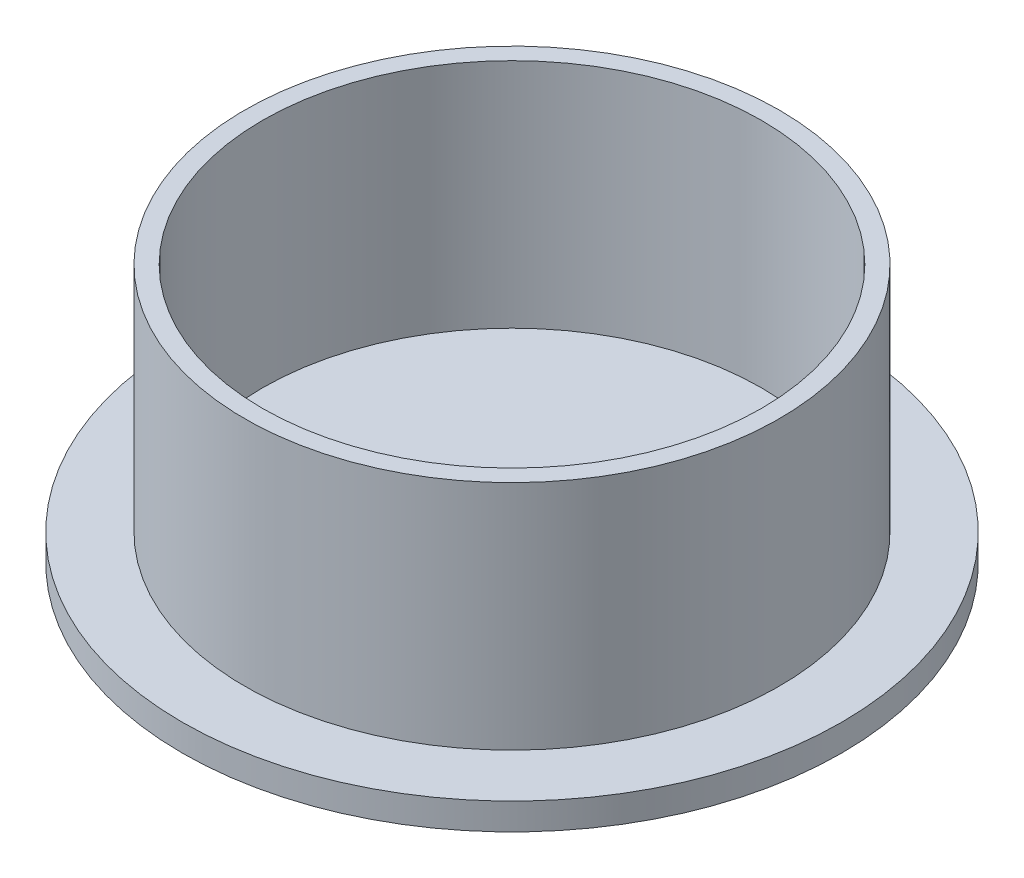
SolidWorks part; units mm, degrees
ref_plane "Front Plane" through (0, 0, 0) normal (0, 0, 1) x (1, 0, 0)
ref_plane "Top Plane" through (0, 0, 0) normal (0, 1, 0) x (1, 0, 0)
ref_plane "Right Plane" through (0, 0, 0) normal (1, 0, 0) x (0, 0, -1)
sketch "Sketch1" plane through (0, 0, 0) normal (0, 1, 0) x (1, 0, 0)
  circle A0 centre (0, 0) radius 37
  circle A1 centre (0, 0) radius 30
  circle A2 centre (0, 0) radius 28
  dimension "D1" = 60
  dimension "D2" = 74
  dimension "D3" = 56
extrude "Boss-Extrude1" add sketch "Sketch1" along normal blind 3 contours A0
extrude "Boss-Extrude2" add sketch "Sketch1<3>" along normal blind 29 contours A1 A2 region at (-29.1515, 0, 0)
sketch "Sketch1<3>" plane through (0, 0, 0) normal (0, 1, 0) x (1, 0, 0) same geometry as "Sketch1"
sketch "Sketch2" plane through (0, 3, 0) normal (0, 1, 0) x (1, 0, 0)
  circle A0 centre (0, 0) radius 4
  circle A1 centre (8, 0) radius 2
  circle A2 centre (0, -8) radius 2
  circle A3 centre (-8, 0) radius 2
  circle A4 centre (0, 8) radius 2
  point P14 (0, 0)
  dimension "D1" = 8
  dimension "D2" = 4
  dimension "D3" = 8
  dimension "D4" = 4
extrude "Cut-Extrude1" cut sketch "Sketch2" against normal through all
